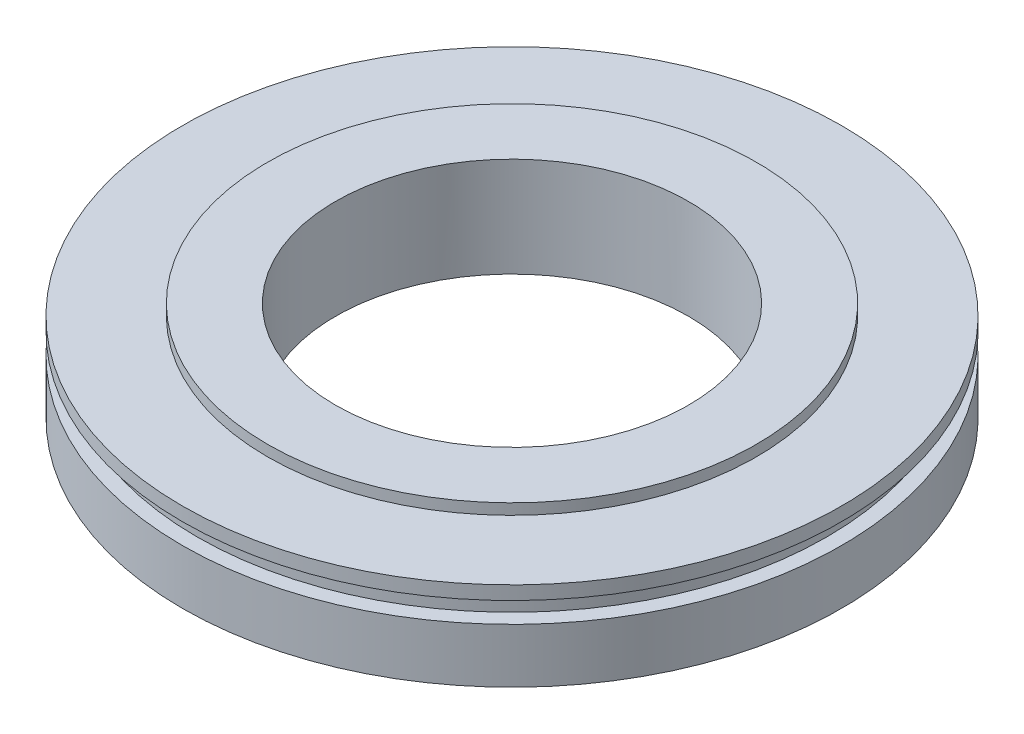
SolidWorks part; units mm, degrees
material "6061-T6 (SS)"
ref_plane "X-Y Datum" through (0, 0, 0) normal (0, 0, 1) x (1, 0, 0)
ref_plane "X-Z Datum" through (0, 0, 0) normal (0, 1, 0) x (1, 0, 0)
ref_plane "Y-Z Datum" through (0, 0, 0) normal (1, 0, 0) x (0, 0, -1)
sketch "Sketch1" plane through (0, 0, 0) normal (1, 0, 0) x (0, 0, -1)
  line L0 (-16.51, 2.6941) -> (-16.51, -5.0208)
  line L1 (-16.51, -5.0208) -> (-30.8229, -5.0208)
  line L4 (-29.4386, -0.5063) -> (-29.4386, 1.4241)
  line L7 (-30.8229, 2.6941) -> (-16.51, 2.6941)
  line L8 (0, 0) -> (0, -47872.0541) construction
  line L9 (0, 0) -> (-47872.0541, 0) construction
  line L10 (-30.8229, -0.5063) -> (-30.8229, -5.0208)
  line L11 (-14.7421, 2.6941) -> (15.0495, 2.6941) construction
  line L12 (-30.9994, 12.7) -> (-30.9994, -12.7) construction
  line L13 (14.2875, -5.0208) -> (-14.2875, -5.0208) construction
  line L15 (-30.8229, 2.6941) -> (-30.8229, 1.4241)
  line L16 (-30.8229, 1.4241) -> (-29.4386, 1.4241)
  line L17 (-29.4386, -0.5063) -> (-30.8229, -0.5063)
  point P15 (-30.9994, 0)
  dimension "D3" = 1.27
  dimension "D1" = 33.02
  dimension "D2" = 61.6458
  dimension "D4" = 1.9304
  dimension "D5" = 25.4
  dimension "D6" = 61.9989
  dimension "D7" = 58.8772
revolve "Revolve1" add sketch "Sketch1" angle 360 about L8
ref_plane "Plane1" through (0, 1.4241, 0) normal (0, 1, 0) x (1, 0, 0)
sketch "Sketch3" plane through (0, 2.6941, 0) normal (0, 1, 0) x (1, 0, 0)
  circle A0 centre (0, 0) radius 30.8229
  circle A1 centre (0, 0) radius 16.51
  circle A2 centre (0, 0) radius 16.51 construction
  circle A4 centre (0, 0) radius 30.8229 construction
extrude "BandAid Solution thicker" add sketch "Sketch3" along normal up to surface (-1.27 mm away) up to plane "Plane1"
sketch "Sketch4" plane through (0, 2.6941, 0) normal (0, 1, 0) x (1, 0, 0)
  circle A0 centre (0, 0) radius 16.51
  circle A1 centre (0, 0) radius 22.86
  circle A3 centre (0, 0) radius 16.51 construction
  dimension "D1" = 45.72
extrude "Lip for Bearing" add sketch "Sketch4" along normal blind 1.016
sketch "Sketch5" plane through (0, -5.0208, 0) normal (0, -1, 0) x (1, 0, 0)
  circle A3 centre (0, 0) radius 16.51
  circle A4 centre (0, 0) radius 30.8229
  circle A5 centre (0, 0) radius 30.8229 construction
  circle A6 centre (0, 0) radius 16.51 construction
extrude "Boss-Extrude1" add sketch "Sketch5" along normal blind 0.5791
